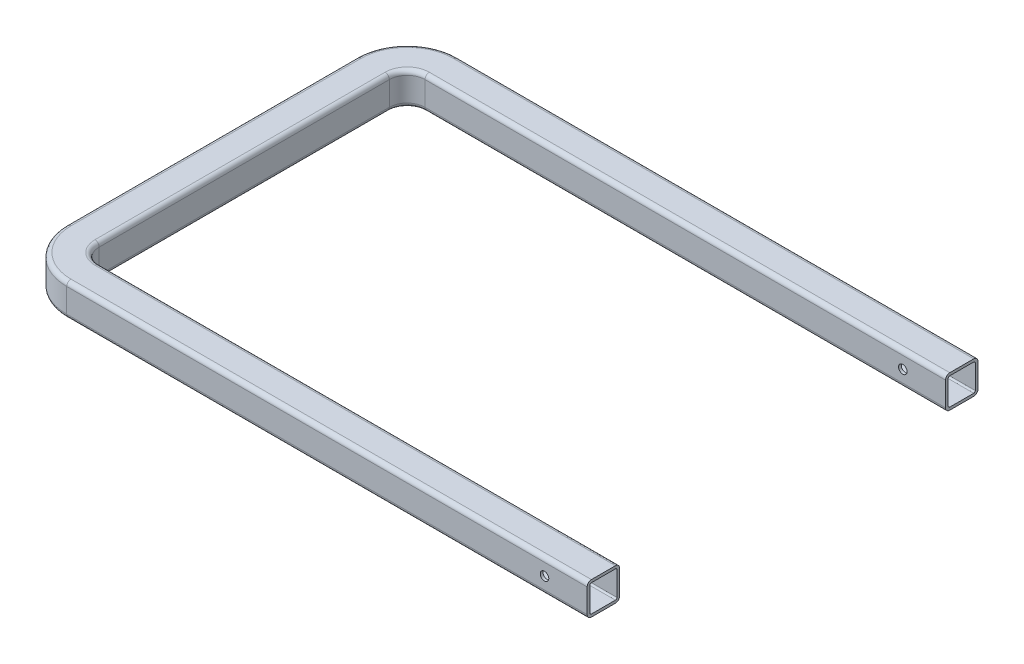
SolidWorks part; units mm, degrees
material "5052-H38, Rod (SS)"
ref_plane "Front Plane" through (0, 0, 0) normal (0, 0, 1) x (1, 0, 0)
ref_plane "Top Plane" through (0, 0, 0) normal (0, 1, 0) x (1, 0, 0)
ref_plane "Right Plane" through (0, 0, 0) normal (1, 0, 0) x (0, 0, -1)
sketch "Sketch1" plane through (0, 0, 0) normal (0, 1, 0) x (1, 0, 0)
  line L0 (0, 0) -> (-610, 0)
  line L1 (-650, 40) -> (-650, 380)
  line L2 (-610, 420) -> (0, 420)
  line L3 (-50, 0) -> (-50, 420) construction
  line L4 (-650, 210) -> (-657.5631, 210) construction
  arc A0 (-610, 0) -> (-650, 40) centre (-610, 40) cw
  arc A1 (-610, 420) -> (-650, 380) centre (-610, 380) ccw
  point P7 (-650, 0)
  point P10 (-650, 420)
  dimension "D3" = 40
  dimension "D1" = 650
  dimension "D2" = 420
  dimension "D4" = 50
sketch "Sketch2" plane through (0, 0, 0) normal (1, 0, 0) x (0, 0, -1)
  line L1 (-14.05, -19.05) -> (14.05, -19.05)
  line L2 (-19.05, -14.05) -> (-19.05, 14.05)
  line L3 (-14.05, 19.05) -> (14.05, 19.05)
  line L4 (19.05, -14.05) -> (19.05, 14.05)
  line L5 (-19.05, -19.05) -> (19.05, 19.05) construction
  line L6 (-19.05, 19.05) -> (19.05, -19.05) construction
  arc A0 (-14.05, 19.05) -> (-19.05, 14.05) centre (-14.05, 14.05) ccw
  arc A1 (-19.05, -14.05) -> (-14.05, -19.05) centre (-14.05, -14.05) ccw
  arc A2 (14.05, -19.05) -> (19.05, -14.05) centre (14.05, -14.05) ccw
  arc A3 (19.05, 14.05) -> (14.05, 19.05) centre (14.05, 14.05) ccw
  point P0 (0, 0)
  dimension "D3" = 5
  dimension "D1" = 38.1
  dimension "D2" = 38.1
sweep "Sweep-Thin1" add profiles "Sketch2" path "Sketch1" parameters "D1"=3.175
sketch "Sketch3" plane through (0, 0, 0) normal (0, 0, 1) x (1, 0, 0)
  line L0 (0, 0) -> (-610, 0) construction
  circle A0 centre (-50, 0) radius 5
  dimension "D1" = 50
extrude "Cut-Extrude1" cut sketch "Sketch3" against normal through all and the other way through all
sketch "Sketch4" plane through (0, 0, -15.875) normal (0, 0, 1) x (1, 0, 0)
  line L0 (0, 0) -> (45, 0) construction
  line L1 (0, -14.05) -> (0, 14.05) construction
  circle A0 centre (-50, 0) radius 5 construction
ref_plane "Plane1" through (-650, 0, 0) normal (1, 0, 0) x (0, 0, -1)
sketch "Sketch5" plane through (-650, 0, 0) normal (1, 0, 0) x (0, 0, -1)
  line L0 (380, 0) -> (38.7593, 0) construction
  line L1 (209.3797, 0) -> (281.8797, 0) construction
  line L3 (209.3797, 0) -> (136.8797, 0) construction
  line L4 (281.8797, 0) -> (281.8797, -50) construction
  line L5 (136.8797, 0) -> (136.8797, -50) construction
  dimension "D1" = 72.5
  dimension "D2" = 72.5
ref_plane "Plane2" through (0, 0, -210) normal (0, 0, -1) x (-1, 0, 0)
